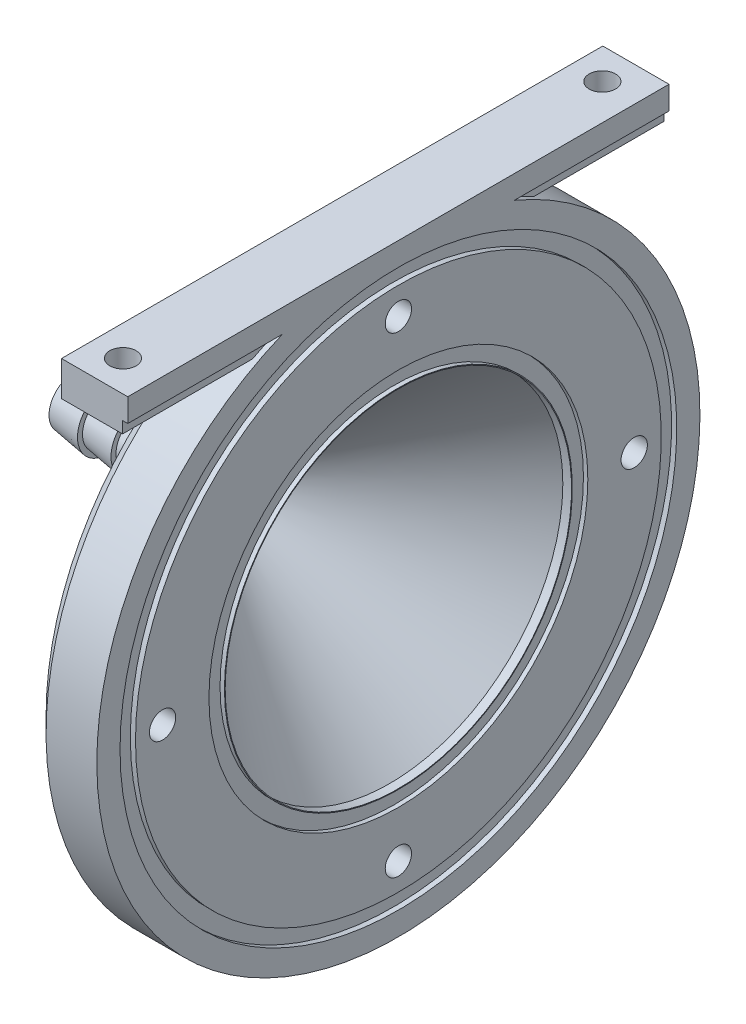
SolidWorks part; units mm, degrees
ref_plane "Front Plane" through (0, 0, 0) normal (0, 0, 1) x (1, 0, 0)
ref_plane "Top Plane" through (0, 0, 0) normal (0, 1, 0) x (1, 0, 0)
ref_plane "Right Plane" through (0, 0, 0) normal (1, 0, 0) x (0, 0, -1)
sketch "Sketch1" plane through (0, 0, 0) normal (0, 0, 1) x (1, 0, 0)
  line L0 (-801.9271, 0) -> (36107.5217, 0) construction
  line L3 (-14.0102, 3.8) -> (-14.0102, 3.15)
  line L8 (-18.3435, 1.9) -> (0, 1.9)
  line L9 (-18.3435, 1.9) -> (-18.3435, 3.15)
  line L10 (23.6874, 24.5) -> (23.6874, 39)
  line L12 (23.6874, 39) -> (15.1214, 39)
  line L16 (23.6874, 24.5) -> (23.1214, 24.5)
  line L17 (23.1214, 24.5) -> (23.1214, 22.4)
  line L18 (15.1214, 39) -> (15.1214, 22.4)
  line L20 (0, 1.9) -> (22.5554, 22.4)
  line L21 (-18.3435, 3.15) -> (-14.0102, 3.8)
  line L22 (22.5554, 22.4) -> (23.1214, 22.4)
  line L23 (-14.0102, 3.15) -> (-9.6768, 3.8)
  line L25 (-9.6768, 3.15) -> (-5.3435, 3.8)
  line L26 (-9.6768, 3.8) -> (-9.6768, 3.15)
  line L27 (-5.3435, 3.8) -> (15.1214, 22.4)
  line L28 (15.1214, 34.5) -> (23.6874, 34.5)
  line L32 (23.1214, 22.5) -> (23.6874, 22.5)
  line L33 (23.6874, 22.5) -> (23.6874, 22.4)
  line L35 (23.6874, 22.4) -> (23.1214, 22.4)
  line L36 (15.1214, 39) -> (23.6874, 39)
  line L38 (23.6874, 36) -> (23.0204, 36)
  line L39 (23.0204, 36) -> (23.0204, 34)
  line L40 (23.0204, 34) -> (23.6874, 34)
  point P20 (0, 0)
  point P22 (0, 0)
  point P23 (23.1214, 22.3487)
  point P28 (23.1214, 22.5)
  point P31 (23.1214, 22.5)
  dimension "D3" = 0.566
  dimension "D2" = 7.6
  dimension "D6" = 3.8
  dimension "D7" = 6.3
  dimension "D5" = 39
  dimension "D8" = 24.5
  dimension "D10" = 2.1
  dimension "D4" = 5
  dimension "D9" = 0.566
  dimension "D11" = 13
  dimension "D12" = 8.566
  dimension "D13" = 4.5
  dimension "D17" = 36
  dimension "D18" = 2
  dimension "D19" = 0.667
  dimension "D14" = 0.1
revolve "Revolve17" add sketch "Sketch1" angle 360 about L0 region at (10.6237, 17.6232, 0) region at (23.4044, 22.45, 0) region at (19.2991, 36.79, 0)
sketch "Sketch4" plane through (15.1214, 0, 0) normal (-1, 0, 0) x (0, 0, 1)
  circle A0 centre (0, 0) radius 30.5 construction
  circle A2 centre (0, 0) radius 39 construction
  point P3 (0, 30.5)
  point P7 (30.5, 0)
  point P12 (-30.5, 0)
  point P13 (0, -30.5)
  dimension "D1" = 8.5
hole_wizard "M3 Clearance Hole1" positions "Sketch4" profile "Sketch5" hole size "M3" standard "ISO"
sketch "Sketch5" plane through (15.1214, -30.5, 0) normal (0, 1, 0) x (0, 0, 1)
  line L0 (0, 0) -> (0, 9.5875)
  line L1 (0, 9.5875) -> (1.7, 8.566)
  line L2 (1.7, 8.566) -> (1.7, 0)
  line L5 (1.7, 0) -> (0, 0)
  line L10 (0, 9.5875) -> (-1.7, 8.566) construction
  line L11 (0, -6.35) -> (0, 107.95) construction
  dimension "Hole Dia." = 3.4
  dimension "Hole Depth" = 8.566
  dimension "Drill Angle" = 118
chamfer "Chamfer1" distance 2 angle 45 1 edges at (15.1214, 0, 39)
extrude "Boss-Extrude1" add sketch "Sketch1<11>" against normal mid plane 70 contours L18 L28 L10 L12 region at (19.2991, 36.79, 0)
sketch "Sketch1<11>" plane through (0, 0, 0) normal (0, 0, 1) x (1, 0, 0) same geometry as "Sketch1"
sketch "Sketch9" plane through (0, 34.5, 0) normal (0, -1, 0) x (-1, 0, 0)
  line L0 (-15.1214, -35) -> (-23.6874, 35) construction
  line L1 (-15.1214, -13.3697) -> (-15.1214, -35) construction
  line L2 (-15.1214, -35) -> (-23.0204, -35) construction
  line L3 (-23.6874, 35) -> (-23.6874, -18.1865) construction
  line L4 (-23.6874, 35) -> (-14.4544, 35) construction
  line L5 (-15.1214, 35) -> (-23.0204, 35) construction
  line L6 (-14.4544, 35) -> (-23.6874, -35) construction
  line L7 (-23.6874, -18.1865) -> (-23.6874, -35) construction
  line L8 (-19.0709, -35) -> (-19.0709, 35) construction
  line L9 (-4.5963, 0) -> (-23.6874, 0) construction
  line L10 (-23.6874, 39) -> (-23.6874, -39) construction
  circle A0 centre (-19.0709, -31) radius 1.7
  circle A1 centre (-19.0709, 31) radius 1.7
  dimension "D1" = 3.4
  dimension "D2" = 4
extrude "Cut-Extrude1" cut sketch "Sketch9" against normal blind 10
sketch "Sketch10" plane through (15.1214, 0, 0) normal (-1, 0, 0) x (0, 0, 1)
  line L0 (37, 0) -> (22.4, 0)
  line L1 (-22.4, 0) -> (-37, 0)
  line L2 (0, -22.4) -> (0, -37)
  circle A1 centre (0, 0) radius 22.4 construction
  point P15 (0, 30.467)
equation "\"D9@Sketch1\"=\"D3@Sketch1\""
